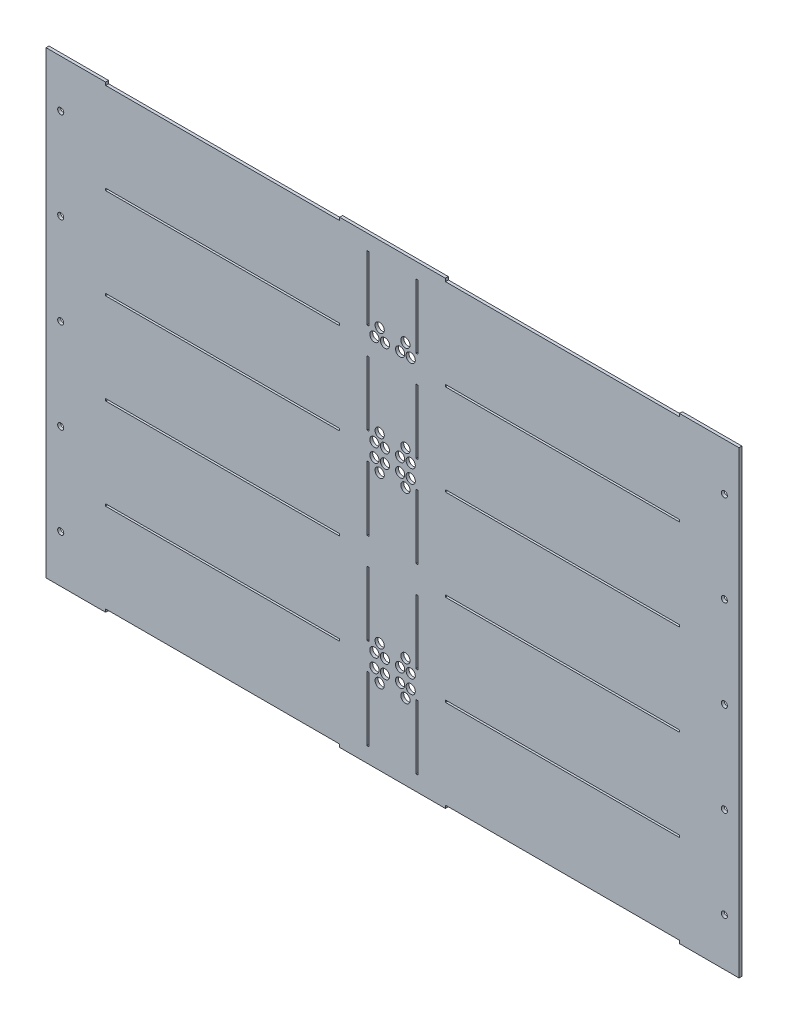
SolidWorks part; units mm, degrees
material "6061-T6 (SS)"
ref_plane "X-Y Datum" through (0, 0, 0) normal (0, 0, 1) x (1, 0, 0)
ref_plane "X-Z Datum" through (0, 0, 0) normal (0, 1, 0) x (1, 0, 0)
ref_plane "Y-Z Datum" through (0, 0, 0) normal (1, 0, 0) x (0, 0, -1)
sketch "Master Sketch" plane through (0, 0, 0) normal (0, 0, 1) x (1, 0, 0)
  line L5 (0, 249.174) -> (0, -249.174) construction
  line L6 (-344.2208, 249.174) -> (344.2208, 249.174)
  line L11 (-344.2208, 249.174) -> (-344.2208, -249.174)
  line L12 (-344.2208, -249.174) -> (344.2208, -249.174)
  line L17 (344.2208, 249.174) -> (344.2208, -249.174)
  line L34 (-344.2208, 249.174) -> (344.2208, -249.174) construction
  line L50 (-344.2208, -249.174) -> (344.2208, 249.174) construction
  line L51 (-25.4, 0) -> (25.4, 0) construction
  line L58 (25.4, 249.174) -> (25.4, -249.174) construction
  line L63 (-25.4, 249.174) -> (-25.4, -249.174) construction
  line L65 (27.686, 50.5714) -> (341.0458, 50.5714) construction
  line L66 (27.686, 245.999) -> (341.0458, 245.999) construction
  line L67 (27.686, 245.999) -> (27.686, 149.4282) construction
  line L68 (27.686, 149.4282) -> (341.0458, 149.4282) construction
  line L69 (341.0458, 245.999) -> (341.0458, 149.4282) construction
  line L70 (27.686, 245.999) -> (341.0458, 149.4282) construction
  line L71 (27.686, 149.4282) -> (341.0458, 245.999) construction
  line L72 (27.686, 147.1422) -> (27.686, 50.5714) construction
  line L73 (27.686, 147.1422) -> (341.0458, 147.1422) construction
  line L74 (341.0458, 147.1422) -> (341.0458, 50.5714) construction
  line L75 (27.686, 147.1422) -> (341.0458, 50.5714) construction
  line L76 (27.686, 50.5714) -> (341.0458, 147.1422) construction
  line L77 (27.686, -48.2854) -> (341.0458, -48.2854) construction
  line L78 (27.686, 48.2854) -> (27.686, -48.2854) construction
  line L79 (27.686, 48.2854) -> (341.0458, 48.2854) construction
  line L80 (341.0458, 48.2854) -> (341.0458, -48.2854) construction
  line L81 (27.686, 48.2854) -> (341.0458, -48.2854) construction
  line L82 (27.686, -48.2854) -> (341.0458, 48.2854) construction
  line L83 (27.686, -147.1422) -> (341.0458, -147.1422) construction
  line L84 (27.686, -50.5714) -> (27.686, -147.1422) construction
  line L85 (27.686, -50.5714) -> (341.0458, -50.5714) construction
  line L86 (341.0458, -50.5714) -> (341.0458, -147.1422) construction
  line L87 (27.686, -50.5714) -> (341.0458, -147.1422) construction
  line L88 (27.686, -147.1422) -> (341.0458, -50.5714) construction
  line L89 (27.686, -245.999) -> (341.0458, -245.999) construction
  line L90 (27.686, -149.4282) -> (27.686, -245.999) construction
  line L91 (27.686, -149.4282) -> (341.0458, -149.4282) construction
  line L92 (341.0458, -149.4282) -> (341.0458, -245.999) construction
  line L93 (27.686, -149.4282) -> (341.0458, -245.999) construction
  line L94 (27.686, -245.999) -> (341.0458, -149.4282) construction
  line L95 (0, -55) -> (0, 55) construction
  line L96 (-341.0458, -149.4282) -> (-341.0458, -245.999) construction
  line L97 (-27.686, -245.999) -> (-341.0458, -245.999) construction
  line L98 (-27.686, -149.4282) -> (-341.0458, -245.999) construction
  line L99 (-27.686, -245.999) -> (-341.0458, -149.4282) construction
  line L100 (-27.686, -149.4282) -> (-341.0458, -149.4282) construction
  line L101 (-27.686, -149.4282) -> (-27.686, -245.999) construction
  line L102 (-341.0458, -50.5714) -> (-341.0458, -147.1422) construction
  line L103 (-27.686, -50.5714) -> (-341.0458, -147.1422) construction
  line L104 (-27.686, -147.1422) -> (-341.0458, -50.5714) construction
  line L105 (-27.686, -147.1422) -> (-341.0458, -147.1422) construction
  line L106 (-27.686, -50.5714) -> (-27.686, -147.1422) construction
  line L107 (-27.686, -50.5714) -> (-341.0458, -50.5714) construction
  line L108 (-341.0458, 48.2854) -> (-341.0458, -48.2854) construction
  line L109 (-27.686, -48.2854) -> (-341.0458, -48.2854) construction
  line L110 (-27.686, -48.2854) -> (-341.0458, 48.2854) construction
  line L111 (-27.686, 48.2854) -> (-341.0458, -48.2854) construction
  line L112 (-27.686, 48.2854) -> (-341.0458, 48.2854) construction
  line L113 (-27.686, 48.2854) -> (-27.686, -48.2854) construction
  line L114 (-341.0458, 147.1422) -> (-341.0458, 50.5714) construction
  line L115 (-27.686, 50.5714) -> (-341.0458, 147.1422) construction
  line L116 (-27.686, 50.5714) -> (-341.0458, 50.5714) construction
  line L117 (-27.686, 147.1422) -> (-341.0458, 50.5714) construction
  line L118 (-27.686, 147.1422) -> (-27.686, 50.5714) construction
  line L119 (-27.686, 147.1422) -> (-341.0458, 147.1422) construction
  line L120 (-341.0458, 245.999) -> (-341.0458, 149.4282) construction
  line L121 (-27.686, 149.4282) -> (-341.0458, 149.4282) construction
  line L122 (-27.686, 149.4282) -> (-341.0458, 245.999) construction
  line L123 (-27.686, 245.999) -> (-27.686, 149.4282) construction
  line L124 (-27.686, 245.999) -> (-341.0458, 149.4282) construction
  line L125 (-27.686, 245.999) -> (-341.0458, 245.999) construction
  point P0 (0, 0)
  point P9 (0, 0)
  point P13 (0, 0)
  point P16 (25.4, 0)
  point P18 (-25.4, 0)
  point P19 (184.3659, 197.7136)
  dimension "D1" = 498.348
  dimension "D2" = 50.8
  dimension "D3" = 313.3598
  dimension "D4" = 96.5708
  dimension "D5" = 3.175
  dimension "D6" = 3.175
  dimension "D7" = 2.286
  dimension "D8" = 5
  dimension "D9" = 2.286
  dimension "D10" = 688.4416
extrude "Boss-Extrude1" add sketch "Master Sketch" along normal blind 3.175
sketch "Sketch1" plane through (0, 0, 3.175) normal (0, 0, 1) x (1, 0, 0)
  line L0 (344.2208, 249.174) -> (-344.2208, 249.174) construction
  line L1 (-344.2208, -249.174) -> (-375.9708, -249.174)
  line L2 (-344.2208, -249.174) -> (-344.2208, 249.174)
  line L3 (-344.2208, 249.174) -> (-375.9708, 249.174)
  line L4 (-375.9708, -249.174) -> (-375.9708, 249.174)
  line L5 (-360.0958, 249.174) -> (-360.0958, -249.174) construction
  line L6 (0, 361.953) -> (0, -361.953) construction
  line L7 (-520.6133, 0) -> (520.6133, 0) construction
  circle A0 centre (-360.0958, 0) radius 3 construction
  circle A1 centre (-360.0958, 98.806) radius 3 construction
  circle A2 centre (-360.0958, 197.612) radius 3 construction
  circle A3 centre (-360.0958, 0) radius 3 construction
  circle A4 centre (-360.0958, 98.806) radius 3 construction
  circle A5 centre (-360.0958, -98.806) radius 3 construction
  circle A6 centre (-360.0958, 0) radius 3 construction
  circle A7 centre (-360.0958, -98.806) radius 3 construction
  circle A8 centre (-360.0958, -197.612) radius 3 construction
  point P13 (0, 0)
  point P17 (0, 0)
  point P20 (0, 0)
  line M8 (-344.2208, 249.174) -> (-344.2208, -249.174)
  dimension "D2" = 6
  dimension "D1" = 31.75
  dimension "D4" = 98.806
  dimension "D5" = 98.806
  dimension "D6" = 3
  dimension "D3" = 3
extrude "Boss-Extrude2" add sketch "Sketch1" against normal blind 3.175 contours L4 L1 L3 A7 A4 A3 M8 region at (-360.0958, 0, 3.175)
hole_wizard "M6 Clearance Hole1" positions "Sketch2" profile "Sketch3" hole size "M6" standard "ANSI Metric" end condition through all
sketch "Sketch2" plane through (0, 0, 3.175) normal (0, 0, 1) x (1, 0, 0)
  point P0 (-360.0958, -197.612)
  point P3 (-360.0958, -98.806)
  point P6 (-360.0958, 0)
  point P9 (-360.0958, 98.806)
  point P12 (-360.0958, 197.612)
sketch "Sketch3" plane through (-360.0958, -197.612, 3.175) normal (1, 0, 0) x (0, -1, 0)
  line L0 (0, 0) -> (0, 3.175)
  line L1 (0, 3.175) -> (3.3, 3.175)
  line L2 (3.3, 3.175) -> (3.3, 0)
  line L5 (3.3, 0) -> (0, 0)
  line L11 (0, -6.35) -> (0, 107.95) construction
  dimension "Thru Hole Dia." = 6.6
  dimension "Thru Hole Depth" = 3.175
mirror "Mirror1" about plane through (0, 0, 0) normal (1, 0, 0) of "M6 Clearance Hole1", "Boss-Extrude2"
sketch "Sketch5" plane through (0, 0, 3.175) normal (0, 0, 1) x (1, 0, 0)
  line L0 (-184.3659, 197.7136) -> (184.3659, 197.7136) construction
  line L1 (-27.686, 149.4282) -> (-341.0458, 245.999) construction
  line L2 (27.686, 245.999) -> (27.686, 149.4282) construction
  line L3 (25.4, 197.7136) -> (27.686, 197.7136) construction
  line L4 (25.4, 249.174) -> (25.4, -249.174) construction
  line L5 (27.686, 197.7136) -> (26.543, 197.7136) construction
  line L6 (26.543, 197.7136) -> (26.543, 199.1948) construction
  line L7 (0, -55) -> (0, 55) construction
  line L8 (25.4, 232.6386) -> (27.686, 232.6386)
  line L9 (25.4, 232.6386) -> (25.4, 162.7886)
  line L10 (25.4, 162.7886) -> (27.686, 162.7886)
  line L11 (27.686, 232.6386) -> (27.686, 162.7886)
  line L12 (25.4, 232.6386) -> (27.686, 162.7886) construction
  line L13 (25.4, 162.7886) -> (27.686, 232.6386) construction
  line L14 (-25.4, 232.6386) -> (-27.686, 232.6386)
  line L15 (-25.4, 162.7886) -> (-27.686, 162.7886)
  line L16 (-25.4, 232.6386) -> (-25.4, 162.7886)
  line L17 (-27.686, 232.6386) -> (-27.686, 162.7886)
  dimension "D1" = 2.286
  dimension "D2" = 69.85
extrude "Cut-Extrude1" cut sketch "Sketch5" against normal through all
pattern_linear "LPattern1" count 5 spacing 98.8568 along (0, -1, 0) of "Cut-Extrude1"
sketch "Sketch6" plane through (0, 0, 3.175) normal (0, 0, 1) x (1, 0, 0)
  line L0 (-184.3659, 245.999) -> (-184.3659, 249.174) construction
  line L1 (-27.686, 245.999) -> (-341.0458, 245.999) construction
  line L2 (-344.2208, 249.174) -> (344.2208, 249.174) construction
  line L3 (0, -55) -> (0, 55) construction
  line L4 (-311.3659, 249.174) -> (-57.3659, 249.174)
  line L5 (-311.3659, 249.174) -> (-311.3659, 245.999)
  line L6 (-311.3659, 245.999) -> (-57.3659, 245.999)
  line L7 (-57.3659, 249.174) -> (-57.3659, 245.999)
  line L8 (-311.3659, 249.174) -> (-57.3659, 245.999) construction
  line L9 (-311.3659, 245.999) -> (-57.3659, 249.174) construction
  line L10 (57.3659, 249.174) -> (57.3659, 245.999)
  line L11 (311.3659, 245.999) -> (57.3659, 245.999)
  line L12 (311.3659, 249.174) -> (311.3659, 245.999)
  line L13 (311.3659, 249.174) -> (57.3659, 249.174)
  point P6 (-184.3659, 247.5865)
  dimension "D1" = 3.175
  dimension "D2" = 254
extrude "Cut-Extrude2" cut sketch "Sketch6" against normal through all
mirror "Mirror2" about plane through (0, 0, 0) normal (0, 1, 0) of "Cut-Extrude2"
sketch "Sketch7" plane through (0, 0, 3.175) normal (0, 0, 1) x (1, 0, 0)
  line L0 (-184.3659, 149.4282) -> (-184.3659, 147.1422) construction
  line L1 (-27.686, 149.4282) -> (-341.0458, 149.4282) construction
  line L2 (-27.686, 147.1422) -> (-341.0458, 147.1422) construction
  line L3 (0, -55) -> (0, 55) construction
  line L4 (-311.3659, 149.4282) -> (-57.3659, 149.4282)
  line L5 (-311.3659, 149.4282) -> (-311.3659, 147.1422)
  line L6 (-311.3659, 147.1422) -> (-57.3659, 147.1422)
  line L7 (-57.3659, 149.4282) -> (-57.3659, 147.1422)
  line L8 (-311.3659, 149.4282) -> (-57.3659, 147.1422) construction
  line L9 (-311.3659, 147.1422) -> (-57.3659, 149.4282) construction
  line L10 (57.3659, 149.4282) -> (57.3659, 147.1422)
  line L11 (311.3659, 149.4282) -> (311.3659, 147.1422)
  line L12 (311.3659, 147.1422) -> (57.3659, 147.1422)
  line L13 (311.3659, 149.4282) -> (57.3659, 149.4282)
  point P6 (-184.3659, 148.2852)
  dimension "D1" = 2.286
  dimension "D2" = 254
extrude "Cut-Extrude3" cut sketch "Sketch7" against normal through all
pattern_linear "LPattern2" count 4 spacing 98.8568 along (0, -1, 0) of "Cut-Extrude3"
sketch "Sketch8" plane through (0, 0, 0) normal (0, 0, -1) x (-1, 0, 0)
  line L0 (8.255, -155.5919) -> (19.685, -155.5919)
  line L1 (13.97, -167.0219) -> (13.97, -155.5919)
  line L2 (25.4, -232.6386) -> (25.4, -162.7886) construction
  line L3 (25.4, -162.7886) -> (27.686, -162.7886) construction
  line L4 (-57.3659, -148.2852) -> (57.3659, -148.2852) construction
  line L5 (-57.3659, -147.1422) -> (-57.3659, -149.4282) construction
  line L6 (57.3659, -149.4282) -> (57.3659, -147.1422) construction
  circle A0 centre (8.255, -155.5919) radius 5
  circle A2 centre (19.685, -155.5919) radius 5
  circle A3 centre (13.97, -167.0219) radius 5
  circle A4 centre (19.685, -140.9785) radius 5
  circle A5 centre (13.97, -129.5485) radius 5
  circle A6 centre (8.255, -140.9785) radius 5
  dimension "D1" = 10
  dimension "D2" = 11.43
  dimension "D3" = 11.43
  dimension "D4" = 11.43
  dimension "D5" = 4.2333
extrude "Cut-Extrude4" cut sketch "Sketch8" against normal through all contours A2 | A0 | A3 region at (-19.685, -150.7334, 0) region at (-17.4055, -163.5864, 0) region at (-3.3964, -155.5919, 0)
mirror "Mirror3" about plane through (0, 0, 0) normal (1, 0, 0) of "Cut-Extrude4"
pattern_linear "LPattern3" count 2 spacing 197.7136 along (0, 1, 0) of "Cut-Extrude4", "Mirror3"
sketch "Sketch9" plane through (0, 0, 0) normal (0, 0, -1) x (-1, 0, 0)
  line L0 (13.97, -167.0219) -> (13.97, -155.5919) construction
  line L1 (8.255, -155.5919) -> (19.685, -155.5919) construction
  line L2 (13.97, -167.0219) -> (13.97, -155.5919)
  line L3 (8.255, -155.5919) -> (19.685, -155.5919)
  circle A1 centre (8.255, -140.9785) radius 5
  circle A2 centre (8.255, -140.9785) radius 5
  circle A3 centre (13.97, -129.5485) radius 5
  circle A4 centre (13.97, -129.5485) radius 5
  circle A5 centre (19.685, -140.9785) radius 5
  circle A6 centre (19.685, -140.9785) radius 5
  circle A7 centre (13.97, -167.0219) radius 5
  circle A8 centre (13.97, -167.0219) radius 5
  circle A9 centre (19.685, -155.5919) radius 5
  circle A10 centre (19.685, -155.5919) radius 5
  circle A11 centre (8.255, -155.5919) radius 5
  circle A12 centre (8.255, -155.5919) radius 5
  dimension "D1" = 0
  dimension "D2" = 0
  dimension "D3" = 0
  dimension "D4" = 0
  dimension "D5" = 0
  dimension "D6" = 0
extrude "Cut-Extrude5" cut sketch "Sketch9" against normal through all contours A2 | A4 | A6 region at (-8.255, -140.9785, 0) region at (-13.97, -129.5485, 0) region at (-19.685, -140.9785, 0)
mirror "Mirror4" about plane through (0, 0, 0) normal (1, 0, 0) of "Cut-Extrude5"
pattern_linear "LPattern4" count 4 spacing 98.8568 along (0, 1, 0) skipping (1, 0) of "Mirror4"
